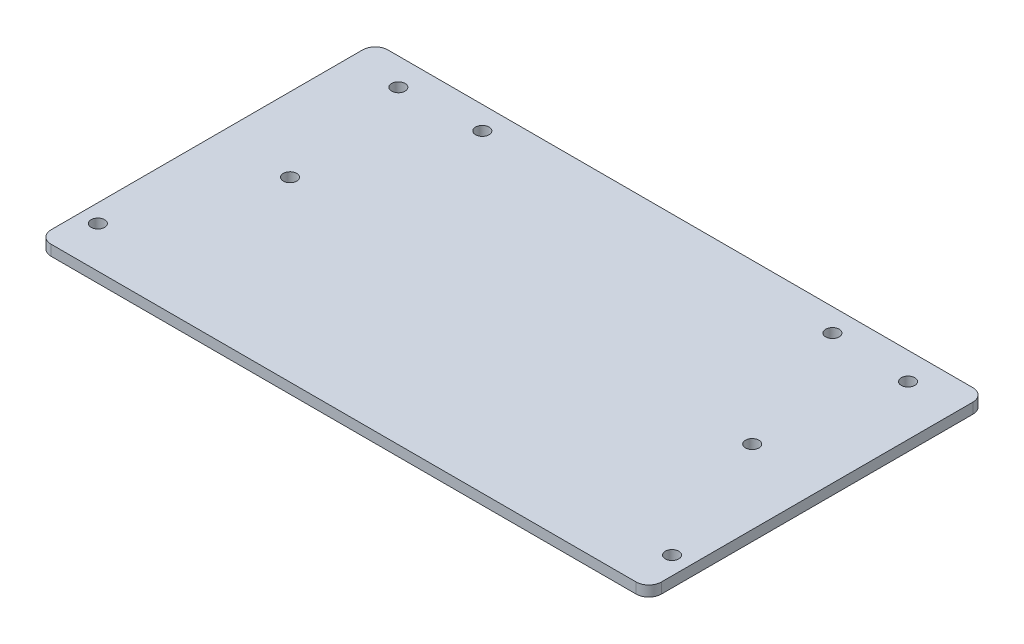
SolidWorks part; units mm, degrees
ref_plane "Front Plane" through (0, 0, 0) normal (0, 0, 1) x (1, 0, 0)
ref_plane "Top Plane" through (0, 0, 0) normal (0, 1, 0) x (1, 0, 0)
ref_plane "Right Plane" through (0, 0, 0) normal (1, 0, 0) x (0, 0, -1)
sketch "Sketch1" plane through (0, 0, 0) normal (0, 1, 0) x (1, 0, 0)
  line L0 (0, 0) -> (0, -101.6)
  line L1 (0, -101.6) -> (184.15, -101.6)
  line L2 (184.15, -101.6) -> (184.15, 0)
  line L3 (184.15, 0) -> (0, 0)
  dimension "D1" = 184.15
  dimension "D3" = 101.6
extrude "Boss-Extrude1" add sketch "Sketch1" along normal blind 3.175 contours L2 L3 L0 L1 region at (92.075, 0, 50.8)
fillet "Fillet1" radius 3.81 4 edges at (184.15, 1.5875, 0) (184.15, 1.5875, 101.6) (0, 1.5875, 0) (0, 1.5875, 101.6)
sketch "Sketch2" plane through (0, 3.175, 0) normal (0, 1, 0) x (1, 0, 0)
  line L0 (92.075, 0) -> (92.075, -101.6) construction
  line L1 (180.34, 0) -> (3.81, 0) construction
  line L2 (3.81, -101.6) -> (180.34, -101.6) construction
  circle A4 centre (5.4374, -89.1463) radius 2.032 construction
  circle A5 centre (5.4374, -89.1463) radius 2.032
  circle A6 centre (22.3389, -48.035) radius 2.032 construction
  circle A7 centre (39.2404, -6.9237) radius 2.032 construction
  circle A8 centre (15.1663, -8.1952) radius 2.032 construction
  circle A9 centre (22.3389, -48.035) radius 2.032
  circle A10 centre (39.2404, -6.9237) radius 2.032
  circle A11 centre (15.1663, -8.1952) radius 2.032
  circle A12 centre (178.7126, -89.1463) radius 2.032
  circle A13 centre (161.8111, -48.035) radius 2.032
  circle A14 centre (168.9837, -8.1952) radius 2.032
  circle A15 centre (144.9096, -6.9237) radius 2.032
extrude "Cut-Extrude1" cut sketch "Sketch2" against normal through all contours A11 | A9 | A5 | A12 | A13 | A15 | A14 | A10 region at (5.4374, 3.175, 89.1463) region at (22.3389, 3.175, 48.035) region at (15.1663, 3.175, 8.1952) region at (178.7126, 3.175, 89.1463) region at (161.8111, 3.175, 48.035) region at (168.9837, 3.175, 8.1952) region at (144.9096, 3.175, 6.9237)
